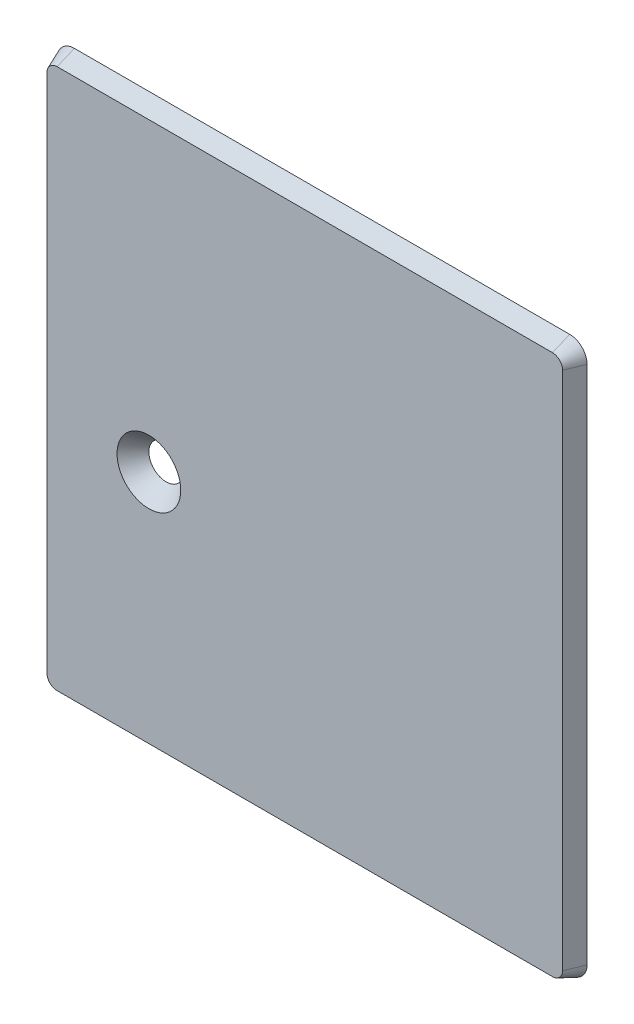
SolidWorks part; units mm, degrees
ref_plane "Front Plane" through (0, 0, 0) normal (0, 0, 1) x (1, 0, 0)
ref_plane "Top Plane" through (0, 0, 0) normal (0, 1, 0) x (1, 0, 0)
ref_plane "Right Plane" through (0, 0, 0) normal (1, 0, 0) x (0, 0, -1)
sketch "Sketch1" plane through (0, 0, 5.066) normal (0, 0, 1) x (1, 0, 0)
  line L1 (-0.6, 60.0604) -> (56.6, 60.0604)
  line L2 (-2.6, 58.0604) -> (-2.6, -2)
  line L3 (-0.6, -4) -> (56.6, -4)
  line L4 (58.6, 58.0604) -> (58.6, -2)
  arc A0 (-2.6, 58.0604) -> (-0.6, 60.0604) centre (-0.6, 58.0604) cw
  arc A1 (58.6, 58.0604) -> (56.6, 60.0604) centre (56.6, 58.0604) ccw
  arc A2 (56.6, -4) -> (58.6, -2) centre (56.6, -2) ccw
  arc A3 (-0.6, -4) -> (-2.6, -2) centre (-0.6, -2) cw
  arc A4 (11.7501, 24) -> (8.2501, 24) centre (10.0001, 24) ccw construction
  arc A5 (8.2501, 24) -> (11.7501, 24) centre (10.0001, 24) ccw construction
  arc A6 (11.7501, 24) -> (8.2501, 24) centre (10.0001, 24) ccw construction
  arc A7 (8.2501, 24) -> (11.7501, 24) centre (10.0001, 24) ccw construction
  arc A12 (12.0001, 24) -> (8.0001, 24) centre (10.0001, 24) ccw
  arc A13 (8.0001, 24) -> (12.0001, 24) centre (10.0001, 24) ccw
  dimension "D5" = 2
  dimension "D6" = 2
  dimension "D7" = 2
  dimension "D8" = 2
  dimension "D1" = 4
  dimension "D2" = 2
  dimension "D3" = 4
  dimension "D4" = 2
  dimension "D9" = 0.25
extrude "top" add sketch "Sketch1" against normal blind 2 from offset 1.5 contours A3 L3 A2 L4 A1 L1 A0 L2 A13 A12 | A13 region at (28.0579, 28.0432, 5.066)
draft "button draft" type of draft neutral plane draft angle 40 faces to draft 1 face at (12.0001, 24, 4.566) neutral plane through (0, 0, 4.566) neutral plane normal (0, 0, -1) reverse direction yes parameters "D1"=40
draft "Draft2" type of draft neutral plane draft angle 22.5 faces to draft 8 face at (57.8071, -3.2071, 5.566) face at (58.6, 28.0302, 5.566) face at (57.8071, 59.2675, 5.566) face at (28, 60.0604, 5.566) face at (-1.8071, 59.2675, 5.566) face at (-2.6, 28.0302, 5.566) face at (-1.8071, -3.2071, 5.566) face at (28, -4, 5.566) neutral plane through (0, 0, 4.566) neutral plane normal (0, 0, -1) reverse direction yes parameters "D1"=22.5
